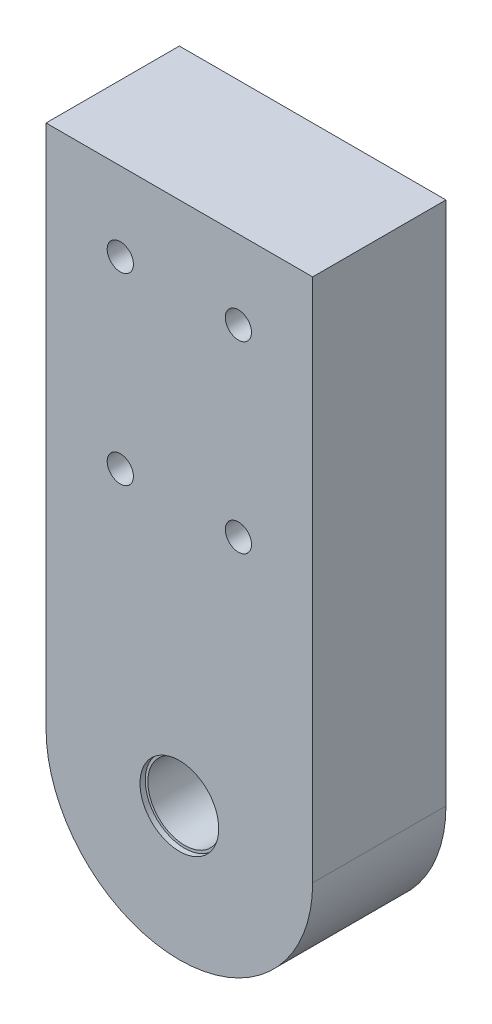
SolidWorks part; units mm, degrees
ref_plane "Front Plane" through (0, 0, 0) normal (0, 0, 1) x (1, 0, 0)
ref_plane "Top Plane" through (0, 0, 0) normal (0, 1, 0) x (1, 0, 0)
ref_plane "Right Plane" through (0, 0, 0) normal (1, 0, 0) x (0, 0, -1)
sketch "Sketch1" plane through (0, 0, 0) normal (0, 0, 1) x (1, 0, 0)
  line L0 (-25.4, 0) -> (-25.4, 100)
  line L1 (-25.4, 100) -> (25.4, 100)
  line L2 (25.4, 100) -> (25.4, 0)
  line L4 (-11.25, 85) -> (11.25, 85) construction
  line L5 (-11.25, 85) -> (-11.25, 50) construction
  line L6 (-11.25, 50) -> (11.25, 50) construction
  line L7 (11.25, 85) -> (11.25, 50) construction
  circle A0 centre (0, 0) radius 7
  arc A1 (-25.4, 0) -> (25.4, 0) centre (0, 0) ccw
  circle A2 centre (-11.25, 85) radius 2.5
  circle A3 centre (11.25, 85) radius 2.5
  circle A4 centre (11.25, 50) radius 2.5
  circle A5 centre (-11.25, 50) radius 2.5
  point P13 (0, 50)
  dimension "D1" = 14
  dimension "D4" = 5
  dimension "D2" = 50.8
  dimension "D3" = 100
  dimension "D5" = 35
  dimension "D6" = 15
  dimension "D7" = 22.5
extrude "Boss-Extrude1" add sketch "Sketch1" along normal blind 25.4
sketch "Sketch2" plane through (0, 0, 25.4) normal (0, 0, 1) x (1, 0, 0)
  circle A0 centre (0, 0) radius 7.5
  dimension "D1" = 15
extrude "Cut-Extrude1" cut sketch "Sketch2" against normal blind 1
sketch "Sketch3" plane through (0, 0, 0) normal (0, 0, -1) x (-1, 0, 0)
  circle A0 centre (0, 0) radius 7.5
  dimension "D1" = 15
extrude "Cut-Extrude2" cut sketch "Sketch3" against normal blind 1
